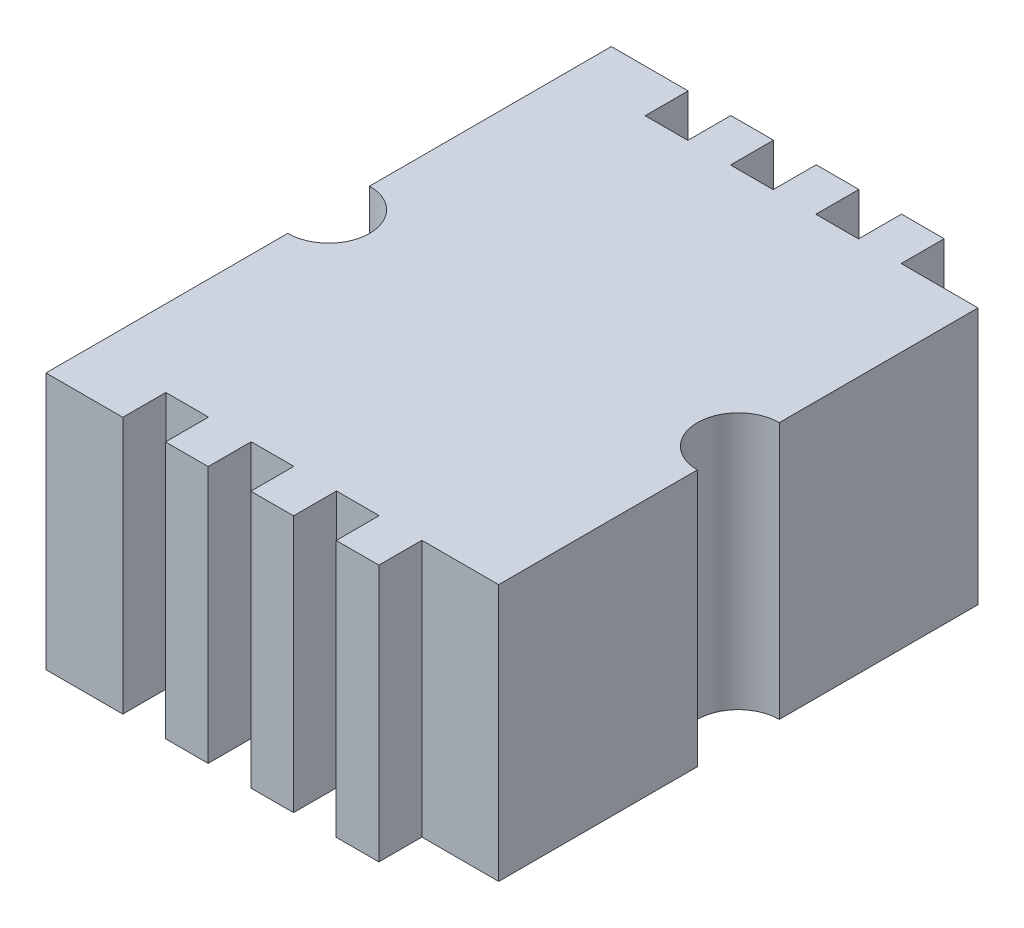
SolidWorks part; units mm, degrees
ref_plane "Front" through (0, 0, 0) normal (0, 0, 1) x (1, 0, 0)
ref_plane "Top" through (0, 0, 0) normal (0, 1, 0) x (1, 0, 0)
ref_plane "Right" through (0, 0, 0) normal (1, 0, 0) x (0, 0, -1)
sketch "Sketch1" plane through (0, 0, 0) normal (0, 1, 0) x (1, 0, 0)
  line L0 (-20, 0) -> (20, 0) construction
  line L1 (20, -14.7) -> (-20, -14.7)
  line L2 (20, -14.7) -> (20, 14.7)
  line L3 (20, 14.7) -> (-20, 14.7)
  line L4 (-20, -14.7) -> (-20, 14.7)
  line L5 (20, -14.7) -> (-20, 14.7) construction
  line L6 (20, 14.7) -> (-20, -14.7) construction
  circle A0 centre (-10, 0) radius 2
  circle A1 centre (10, 0) radius 2
  point P0 (0, 0)
  dimension "D3" = 4
  dimension "D4" = 4
  dimension "D1" = 29.4
  dimension "D2" = 40
  dimension "D5" = 10
  dimension "D6" = 10
extrude "Boss-Extrude1" add sketch "Sketch1" along normal blind 20
sketch "Sketch2" plane through (0, 0, -14.7) normal (0, 0, -1) x (-1, 0, 0)
  line L0 (-20, 20) -> (-20, 0) construction
  line L1 (-20, 20) -> (20, 20)
  line L2 (-20, 20) -> (-20, 7.45)
  line L3 (-20, 7.45) -> (20, 7.45)
  line L4 (20, 20) -> (20, 7.45)
  line L5 (0, 7.45) -> (0, 20) construction
  line L6 (-20, 13.725) -> (20, 13.725) construction
  line L7 (20, 20) -> (20, 0) construction
  line L8 (-20, 0) -> (20, 0) construction
  line L9 (-20, 20) -> (20, 20) construction
  line L10 (-20, 0) -> (-10, 0)
  line L11 (-20, 0) -> (-20, 20)
  line L12 (-20, 20) -> (-10, 20)
  line L13 (-10, 0) -> (-10, 20)
  line L14 (-15, 20) -> (-15, 0) construction
  line L15 (-20, 10) -> (-10, 10) construction
  line L17 (20, 0) -> (10, 0)
  line L18 (20, 0) -> (20, 20)
  line L19 (20, 20) -> (10, 20)
  line L20 (10, 0) -> (10, 20)
  line L21 (15, 20) -> (15, 0) construction
  line L22 (20, 10) -> (10, 10) construction
  point P147 (15, 10)
  point P208 (0, 13.725)
  point P271 (-15, 10)
  line M1 (-20, 0) -> (20, 0)
  line M2 (20, 0) -> (20, 20)
  line M3 (20, 20) -> (-20, 20)
  line M4 (-20, 20) -> (-20, 0)
  dimension "D1" = 7.45
  dimension "D2" = 10
  dimension "D3" = 10
extrude "Cut-Extrude1" cut sketch "Sketch2" against normal blind 3 contours L3 L20 L1 L13 region at (0, 13.725, -14.7)
mirror "Mirror1" about plane through (0, 0, 0) normal (0, 0, 1) of "Cut-Extrude1"
extrude "Cut-Extrude2" cut sketch "Sketch2<3>" against normal up to next contours L13 L3 M1 M4 | L3 L13 L1 M4 | L20 L3 M2 M3 | L20 L3 M1 M2 region at (15, 13.725, -14.7) region at (15, 3.725, -14.7) region at (-15, 13.725, -14.7) region at (-15, 3.725, -14.7)
sketch "Sketch2<3>" plane through (0, 0, -14.7) normal (0, 0, -1) x (-1, 0, 0) same geometry as "Sketch2"
sketch "Sketch4" plane through (0, 20, 0) normal (0, 1, 0) x (1, 0, 0)
  line L0 (6.25, 13.8) -> (6.25, 11.7)
  line L1 (10, 11.7) -> (-10, 11.7)
  line L2 (10, 11.7) -> (10, 13.8)
  line L3 (10, 13.8) -> (-10, 13.8)
  line L4 (-10, 11.7) -> (-10, 13.8)
  line L5 (0, 13.8) -> (0, 11.7) construction
  line L6 (10, 12.75) -> (-10, 12.75) construction
  line L7 (4.1667, 13.8) -> (4.1667, 11.7)
  line L8 (2.0833, 13.8) -> (2.0833, 11.7)
  line L9 (0, 13.8) -> (0, 11.7)
  line L10 (-2.0833, 13.8) -> (-2.0833, 11.7)
  line L11 (-4.1667, 13.8) -> (-4.1667, 11.7)
  line L12 (-6.25, 13.8) -> (-6.25, 11.7)
  point P148 (0, 12.75)
  line M13 (10, 11.7) -> (-10, 11.7)
  dimension "D1" = 2.1
  dimension "D2" = 3.75
  dimension "D3" = 7
extrude "Boss-Extrude2" add sketch "Sketch4" against normal up to next contours L3 L7 L0 M13 | L3 L9 L8 M13 | L3 L11 L10 M13 | L12 L3 L4 M13 region at (5.2083, 20, -12.75) region at (1.0417, 20, -12.75) region at (-3.125, 20, -12.75) region at (-8.125, 20, -12.75)
mirror "Mirror2" about plane through (0, 0, 0) normal (0, 0, 1) of "Boss-Extrude2"
sketch "Sketch5" plane through (0, 0, 0) normal (0, -1, 0) x (1, 0, 0)
  line L1 (10, -14.7) -> (-10, -14.7)
  line L2 (10, -14.7) -> (10, 14.7)
  line L3 (10, 14.7) -> (-10, 14.7)
  line L4 (-10, -14.7) -> (-10, 14.7)
  line L5 (0, 14.7) -> (0, -14.7) construction
  line L6 (10, 0) -> (-10, 0) construction
  point P108 (0, 0)
extrude "Cut-Extrude3" cut sketch "Sketch5" against normal up to vertex (7.45 mm away) up to point (-10, 7.45, -14.7)
